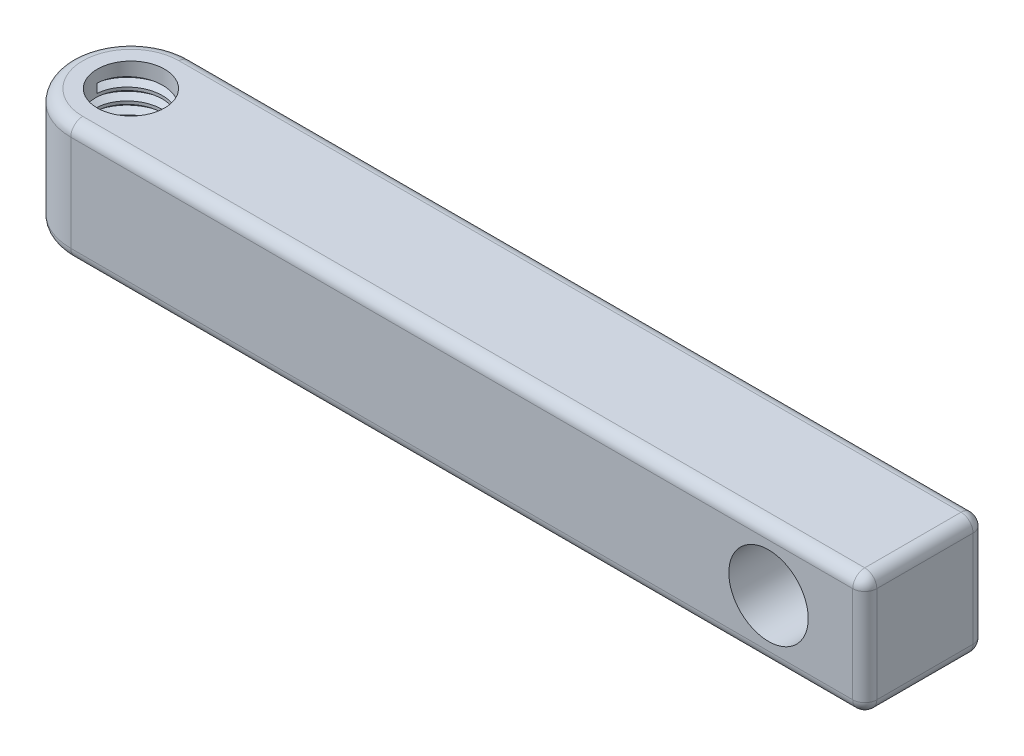
SolidWorks part; units mm, degrees
ref_plane "前视基准面" through (0, 0, 0) normal (0, 0, 1) x (1, 0, 0)
ref_plane "上视基准面" through (0, 0, 0) normal (0, 1, 0) x (1, 0, 0)
ref_plane "右视基准面" through (0, 0, 0) normal (1, 0, 0) x (0, 0, -1)
sketch "草图1" plane through (0, 0, 0) normal (0, 1, 0) x (1, 0, 0)
  line L0 (0, 0) -> (33, 0) construction
  line L1 (0, 2.5) -> (33, 2.5)
  line L2 (0, -2.5) -> (33, -2.5)
  line L3 (33, -2.5) -> (33, 2.5)
  arc A0 (0, 2.5) -> (0, -2.5) centre (0, 0) ccw
  point P3 (12.5, 0)
  dimension "D1" = 5
  dimension "D2" = 33
extrude "凸台-拉伸1" add sketch "草图1" along normal blind 5
sketch "草图2" plane through (0, 5, 0) normal (0, 1, 0) x (1, 0, 0)
  circle A0 centre (0, 0) radius 1.4
  dimension "D1" = 2.8
extrude "切除-拉伸1" cut sketch "草图2" against normal through all
sketch "草图3" plane through (0, 0, 2.5) normal (0, 0, 1) x (1, 0, 0)
  line L0 (0, 0) -> (33, 0) construction
  line L1 (33, 5) -> (33, 0) construction
  circle A0 centre (29, 2.5) radius 1.65
  dimension "D1" = 3.3
  dimension "D2" = 2.5
  dimension "D3" = 4
extrude "切除-拉伸2" cut sketch "草图3" against normal through all
fillet "圆角1" radius 0.5 4 edges at (33, 2.5, 2.5) (33, 5, 0) (33, 2.5, -2.5) (33, 0, 0)
fillet "圆角3" radius 0.5 10 edges at (32.8536, 4.8536, -2.3536) (32.8536, 4.8536, 2.3536) (16.25, 5, 2.5) (-2.5, 5, 0) (32.8536, 0.1464, -2.3536) (32.8536, 0.1464, 2.3536) (16.25, 0, 2.5) (-2.5, 0, 0) (16.25, 5, -2.5) (16.25, 0, -2.5)
thread "螺纹线1" pitch 0.5 method cut profile "螺纹线轮廓1" start angle 0, offset 0.5, length 0, pitch 0.5, diameter 2.8
ref_plane "基准面1" through (-1.4, 4.5, 0) normal (0, 0, 1) x (-1, 0, 0)
sketch "螺纹线轮廓1" plane through (-1.4, 4.5, 0) normal (0, 0, 1) x (-1, 0, 0)
  line L0 (0, 0) -> (0, 0.5) construction
  line L1 (0, 0) -> (0.2706, 0.1562)
  line L2 (0.2706, 0.1562) -> (0.2706, 0.2187)
  line L3 (0.2706, 0.2187) -> (0, 0.375)
  line L4 (0.2706, 0.1875) -> (0, 0.1875) construction
  line L11 (0, 0) -> (0, 0.375)
  point P2 (0, 0)
  dimension "Pitch" = 0.5
  dimension "Profile_Angle" = 60
  dimension "Profile_Land" = 0.0625
  dimension "Profile_Height" = 0.2706
